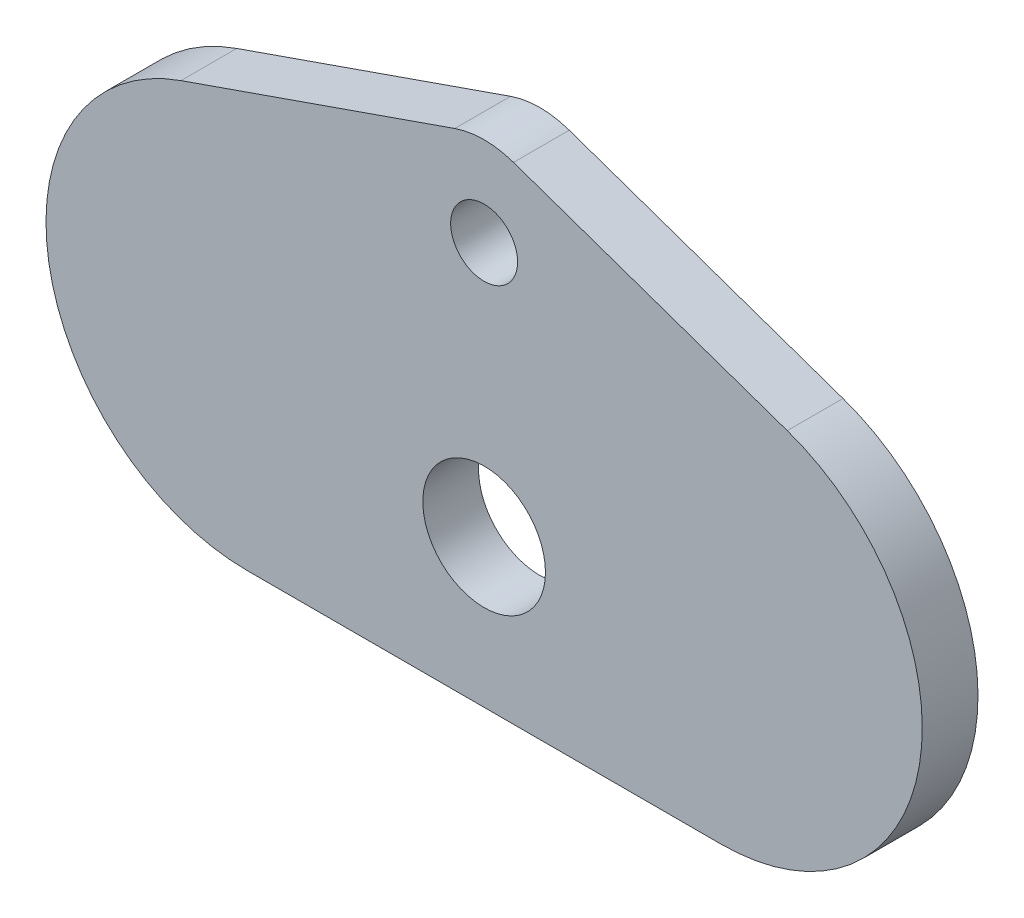
SolidWorks part; units mm, degrees
ref_plane "Płaszczyzna przednia" through (0, 0, 0) normal (0, 0, 1) x (1, 0, 0)
ref_plane "Płaszczyzna górna" through (0, 0, 0) normal (0, 1, 0) x (1, 0, 0)
ref_plane "Płaszczyzna prawa" through (0, 0, 0) normal (1, 0, 0) x (0, 0, -1)
sketch "Sketch1" plane through (0, 0, 0) normal (0, 0, 1) x (1, 0, 0)
  line L0 (-42.5, -52.095) -> (42.5, -52.095) construction
  line L1 (0, -52.095) -> (0, 0) construction
  line L2 (-42.5, -52.095) -> (42.5, -52.095) construction
  line L3 (-42.5, -16) -> (42.5, -16)
  line L4 (-42.5, -88.19) -> (42.5, -88.19)
  line L5 (-5.2663, -0.8915) -> (-54.3806, -18.0113)
  line L6 (5.2663, -0.8915) -> (54.3806, -18.0113)
  circle A0 centre (-42.5, -52.095) radius 26.095
  circle A1 centre (42.5, -52.095) radius 26.095
  circle A4 centre (0, -16) radius 6
  arc A7 (-42.5, -16) -> (-42.5, -88.19) centre (-42.5, -52.095) ccw
  arc A8 (42.5, -88.19) -> (42.5, -16) centre (42.5, -52.095) ccw
  circle A9 centre (0, -16) radius 16
  circle A10 centre (0, -61.6975) radius 11
  point P9 (0, -52.095)
  dimension "D1" = 52.19
  dimension "D2" = 52.19
  dimension "D3" = 42.5
  dimension "D4" = 10
  dimension "D5" = 10
  dimension "D6" = 22
  dimension "D7" = 12
  dimension "D9" = 43.5713
  dimension "D8" = 85
extrude "Boss-Extrude1" add sketch "Sketch1" along normal blind 10 contours A9 L3 A7 L4 A8 A10 A0 A1 | A9 L3 A8 L6 | A9 L5 A7 L3 | L3 A9 A4 | L3 A9 A4 | A0 | A1 region at (0, -8.5149, 0) region at (0, -23.4851, 0) region at (25.6024, -11.5835, 0) region at (29.25, -17.7297, 0) region at (-25.6024, -11.5835, 0) region at (-42.5, -52.095, 0) region at (42.5, -52.095, 0)
